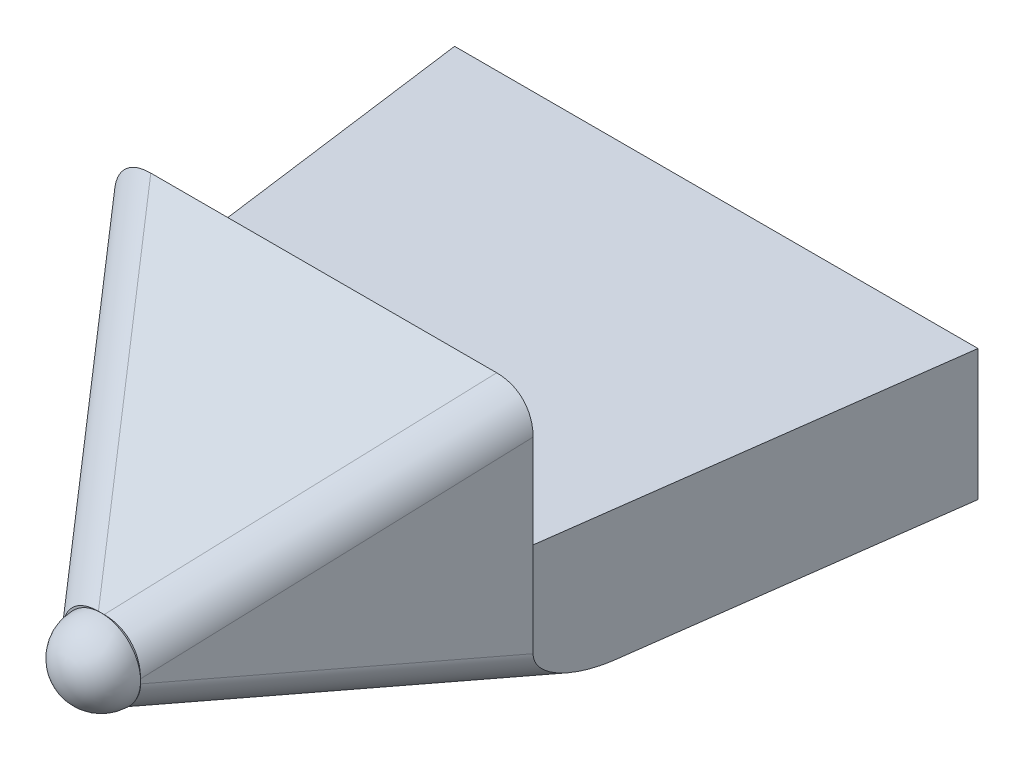
SolidWorks part; units mm, degrees
material "Thornel Mat VMA"
ref_plane "Plan de face" through (0, 0, 0) normal (0, 0, 1) x (1, 0, 0)
ref_plane "Plan de dessus" through (0, 0, 0) normal (0, 1, 0) x (1, 0, 0)
ref_plane "Plan de droite" through (0, 0, 0) normal (1, 0, 0) x (0, 0, -1)
sketch "Esquisse1" plane through (0, 0, 0) normal (1, 0, 0) x (0, 0, -1)
  line L0 (-618.3036, 58.9286) -> (231.6964, 758.9286)
  line L1 (231.6964, 758.9286) -> (231.6964, 258.9286)
  line L2 (231.6964, 258.9286) -> (1731.6964, 258.9286)
  line L3 (1731.6964, 258.9286) -> (1731.6964, -241.0714)
  line L4 (1731.6964, -241.0714) -> (-618.3036, -241.0714)
  arc A0 (-618.3036, -241.0714) -> (-618.3036, 58.9286) centre (-618.3036, -91.0714) cw
  dimension "D4" = 300
  dimension "D1" = 500
  dimension "D2" = 500
  dimension "D3" = 2350
  dimension "D5" = 850
extrude "Boss.-Extru.1" add sketch "Esquisse1" along normal blind 2000
sketch "Esquisse2" plane through (0, 0, 0) normal (0, 1, 0) x (1, 0, 0)
  line L0 (0, -768.3036) -> (850, -768.3036)
  line L1 (2000, 231.6964) -> (0, 231.6964) construction
  line L5 (0, 1731.6964) -> (0, -768.3036)
  line L6 (2000, -618.3036) -> (0, -618.3036) construction
  line L10 (0, -768.3036) -> (2000, -768.3036) construction
  line L17 (0, 1731.6964) -> (200, 231.6964)
  line L18 (200, 231.6964) -> (850, -618.3036)
  line L19 (1000, 1731.6964) -> (1000, -768.3036) construction
  line L20 (2000, 1731.6964) -> (0, 1731.6964) construction
  line L21 (2000, -768.3036) -> (1150, -768.3036)
  line L23 (1800, 231.6964) -> (1150, -618.3036)
  line L24 (2000, 1731.6964) -> (2000, -768.3036)
  line L25 (2000, 1731.6964) -> (1800, 231.6964)
  line L26 (850, -618.3036) -> (1150, -618.3036)
  line L27 (1150, -768.3036) -> (850, -768.3036)
extrude "Enlèv. mat.-Extru.1" cut sketch "Esquisse2" against normal blind 760 and the other way blind 1360
ref_plane "Plan1" through (1000, 0, 0) normal (1, 0, 0) x (0, 0, -1)
sketch "Esquisse4" plane through (1000, 0, 0) normal (1, 0, 0) x (0, 0, -1)
  line L0 (-618.3036, -91.0714) -> (-618.3036, 58.9286)
  line L1 (-618.3036, 58.9286) -> (-618.3036, -241.0714) construction
  line L3 (-768.3036, -91.0714) -> (-618.3036, -91.0714)
  arc A0 (-618.3036, 58.9286) -> (-768.3036, -91.0714) centre (-618.3036, -91.0714) ccw
revolve "Révolution1" add sketch "Esquisse4" angle 360 about L3
fillet "Congé3" radius 140 2 edges at (525, -241.0714, 193.3036) (1475, -241.0714, 193.3036)
fillet "Congé4" radius 180 2 edges at (1475, 408.9286, 193.3036) (525, 408.9286, 193.3036)
sketch "Esquisse5" plane through (0, -241.0714, 0) normal (0, -1, 0) x (1, 0, 0)
  line L0 (1000, -816.0142) -> (122.091, -816.0142) construction
  line L1 (0, -1731.6964) -> (162.781, -510.8391) construction
  line L2 (1000, -816.0142) -> (1877.909, -816.0142) construction
  line L3 (1837.219, -510.8391) -> (2000, -1731.6964) construction
  circle A0 centre (1000, -816.0142) radius 400
  dimension "D1" = 800
  dimension "D2" = 1400
extrude "Enlèv. mat.-Extru.2" cut sketch "Esquisse5" against normal blind 150
